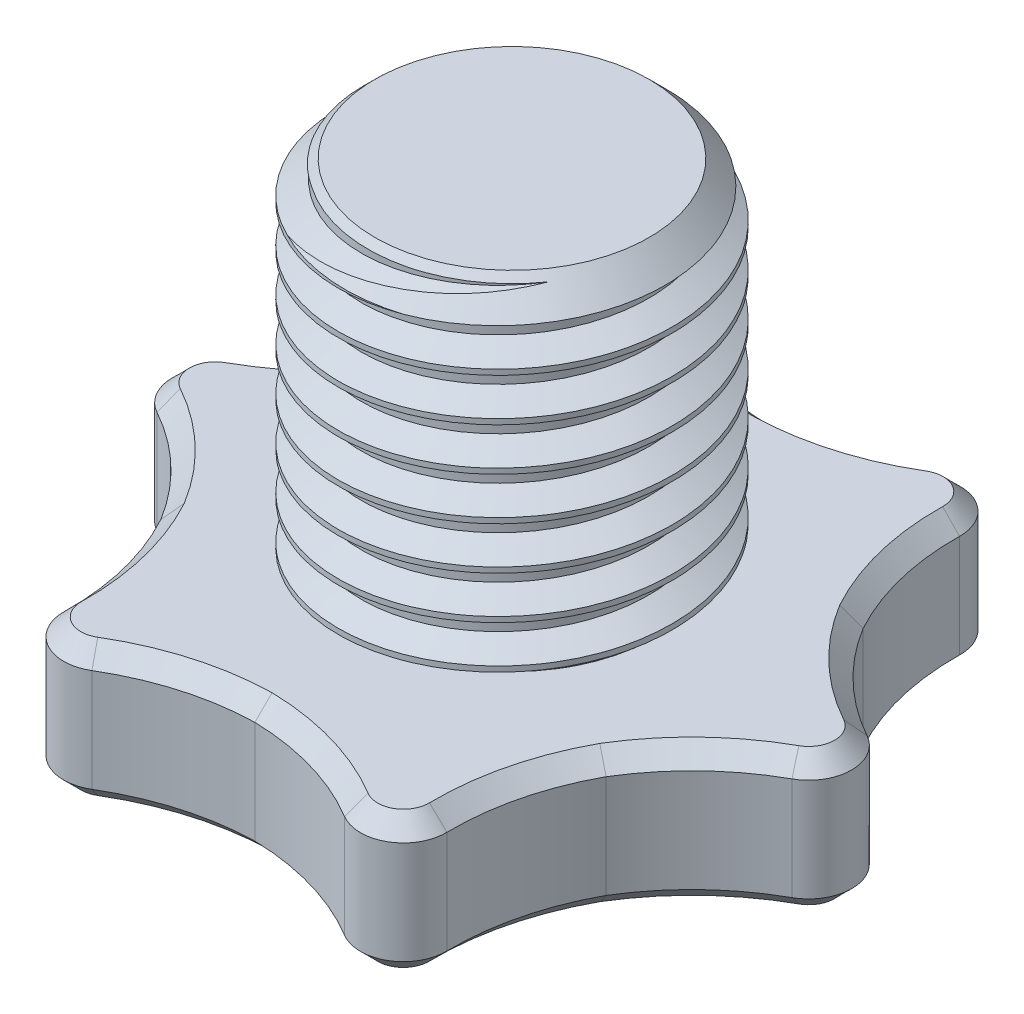
SolidWorks part; units mm, degrees
ref_plane "前视基准面" through (0, 0, 0) normal (0, 0, 1) x (1, 0, 0)
ref_plane "上视基准面" through (0, 0, 0) normal (0, 1, 0) x (1, 0, 0)
ref_plane "右视基准面" through (0, 0, 0) normal (1, 0, 0) x (0, 0, -1)
sketch "草图1" plane through (0, 0, 0) normal (0, 1, 0) x (1, 0, 0)
  line L1 (17.3205, 0) -> (8.6603, 15)
  line L2 (8.6603, 15) -> (-8.6603, 15)
  line L3 (-8.6603, 15) -> (-17.3205, 0)
  line L4 (-17.3205, 0) -> (-8.6603, -15)
  line L5 (-8.6603, -15) -> (8.6603, -15)
  line L6 (8.6603, -15) -> (17.3205, 0)
  circle A0 centre (0, 0) radius 15 construction
  dimension "D1" = 30
extrude "凸台-拉伸1" add sketch "草图1" against normal blind 8
sketch "草图4" plane through (0, -8, 0) normal (0, -1, 0) x (1, 0, 0)
  line L0 (0, 0) -> (-8.6603, 15) construction
  circle A0 centre (-8.6603, 15) radius 2.5
  circle A1 centre (8.6603, 15) radius 2.5
  circle A2 centre (17.3205, 0) radius 2.5
  circle A3 centre (8.6603, -15) radius 2.5
  circle A4 centre (-8.6603, -15) radius 2.5
  circle A5 centre (-17.3205, 0) radius 2.5
  dimension "D1" = 5
  dimension "D3" = 17.3205
  dimension "D2" = 6
extrude "凸台-拉伸3" add sketch "草图4" against normal up to surface (8 mm away) up to face at (0, 0, 0)
fillet "圆角1" radius 15 12 edges at (-9.9103, -4, 12.8349) (-6.1603, -4, 15) (16.0705, -4, -2.1651) (16.0705, -4, 2.1651) (9.9103, -4, 12.8349) (6.1603, -4, 15) (-16.0705, -4, 2.1651) (-16.0705, -4, -2.1651) (-9.9103, -4, -12.8349) (9.9103, -4, -12.8349) (6.1603, -4, -15) (-6.1603, -4, -15)
chamfer "倒角1" distance 1 angle 45 36 edges at (-3.8254, -8, 15.5939) (3.8254, -8, 15.5939) (9.9103, -8, 17.1651) (11.592, -8, 11.1099) (15.4174, -8, 4.484) (19.8205, -8, 0) (15.4174, -8, -4.484) (11.592, -8, -11.1099) (9.9103, -8, -17.1651) (3.8254, -8, -15.5939) (-3.8254, -8, -15.5939) (-9.9103, -8, -17.1651) (-11.592, -8, -11.1099) (-15.4174, -8, -4.484) (-19.8205, -8, 0) (-15.4174, -8, 4.484) (-11.592, -8, 11.1099) (-9.9103, -8, 17.1651) (-19.8205, 0, 0) (-15.4174, 0, -4.484) (-11.592, 0, -11.1099) (-9.9103, 0, -17.1651) (-3.8254, 0, -15.5939) (3.8254, 0, -15.5939) (9.9103, 0, -17.1651) (11.592, 0, -11.1099) (15.4174, 0, -4.484) (19.8205, 0, 0) (15.4174, 0, 4.484) (11.592, 0, 11.1099) (9.9103, 0, 17.1651) (3.8254, 0, 15.5939) (-3.8254, 0, 15.5939) (-9.9103, 0, 17.1651) (-11.592, 0, 11.1099) (-15.4174, 0, 4.484)
sketch "草图2" plane through (0, 0, 0) normal (0, -1, 0) x (-1, 0, 0)
  circle A0 centre (0, 0) radius 9.75
  dimension "D1" = 19.5
extrude "凸台-拉伸2" add sketch "草图2" against normal blind 20
thread "螺纹线1" pitch 2.5 method cut trim with end face yes profile "螺纹线轮廓1" start angle 0, offset 5, length 0, pitch 2.5, diameter 19.5
ref_plane "基准面4" through (-9.75, 25, 0) normal (0, 0, 1) x (-1, 0, 0)
sketch "螺纹线轮廓1" plane through (-9.75, 25, 0) normal (0, 0, 1) x (-1, 0, 0)
  line L0 (0, 0) -> (0, 2.5) construction
  line L11 (0, 0) -> (0, 2.1875)
  line L12 (0, 2.1875) -> (-1.3532, 1.4062)
  line L13 (-1.3532, 1.4062) -> (-1.3532, 0.7812)
  line L15 (-1.3532, 0.7812) -> (0, 0)
  line L17 (-1.3532, 1.0937) -> (0, 1.0937) construction
  point P2 (0, 0)
  dimension "Pitch" = 2.5
  dimension "Profile_Angle" = 60
  dimension "Profile_Land" = 0.625
  dimension "Profile_Height" = 1.3532
sketch "草图5" plane through (0, 0, 0) normal (0, 0, 1) x (1, 0, 0)
  line L0 (8, 20) -> (13, 15)
  line L1 (13, 15) -> (13, 20)
  line L2 (13, 20) -> (8, 20)
  line L3 (8.3968, 20) -> (3.2267, 20) construction
  line L4 (0, 0) -> (0, 50000) construction
  dimension "D1" = 45
  dimension "D2" = 5
  dimension "D3" = 8
revolve "切除-旋转1" cut sketch "草图5" angle 360 about L4
